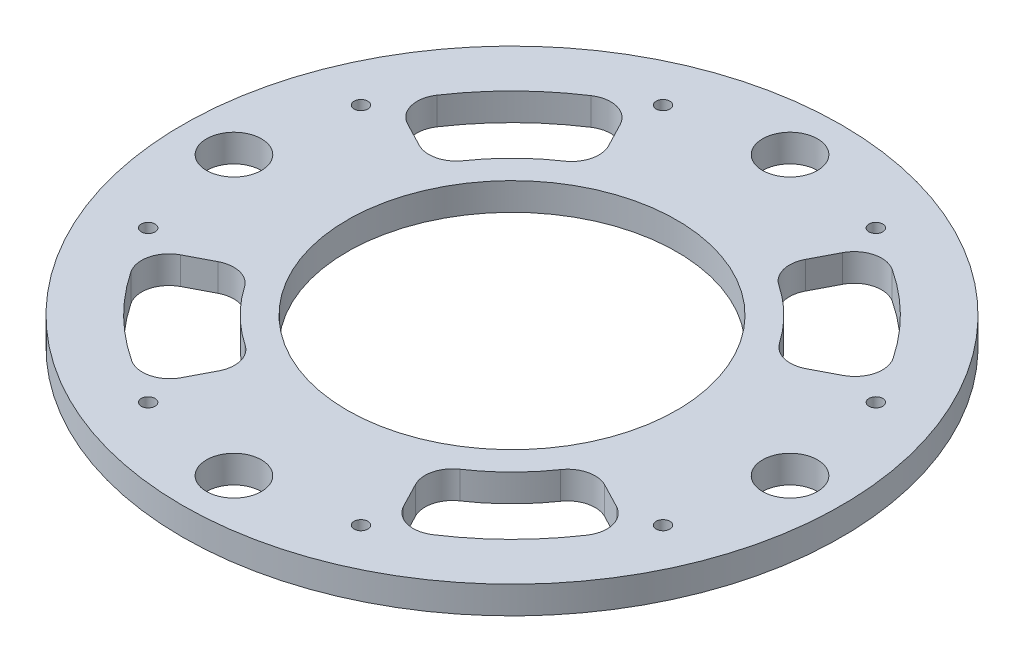
SolidWorks part; units mm, degrees
material "Acrylic (Medium-high impact)"
ref_plane "Front Plane" through (0, 0, 0) normal (0, 0, 1) x (1, 0, 0)
ref_plane "Top Plane" through (0, 0, 0) normal (0, 1, 0) x (1, 0, 0)
ref_plane "Right Plane" through (0, 0, 0) normal (1, 0, 0) x (0, 0, -1)
sketch "Sketch1" plane through (0, 0, 0) normal (0, 1, 0) x (1, 0, 0)
  circle A0 centre (0, 0) radius 76.2
  dimension "D1" = 152.4
extrude "Boss-Extrude1" add sketch "Sketch1" along normal blind 6.35
sketch "Sketch2" plane through (0, 6.35, 0) normal (0, 1, 0) x (1, 0, 0)
  circle A0 centre (0, 0) radius 35
  dimension "D1" = 70
extrude "Cut-Extrude1" cut sketch "Sketch2" against normal blind 6.35
sketch "Sketch3" plane through (0, 6.35, 0) normal (0, 1, 0) x (1, 0, 0)
  line L0 (-76.2, 0) -> (76.2, 0) construction
  line L1 (-51.5875, 51.5875) -> (51.5875, 51.5875) construction
  line L2 (-51.5875, 51.5875) -> (-51.5875, -51.5875) construction
  line L3 (-51.5875, -51.5875) -> (51.5875, -51.5875) construction
  line L4 (51.5875, 51.5875) -> (51.5875, -51.5875) construction
  circle A0 centre (0, 0) radius 76.2 construction
  circle A1 centre (-64.2875, 0) radius 6.35
  circle A2 centre (64.2875, 0) radius 6.35
  dimension "D1" = 12.7
  dimension "D2" = 12.7
  dimension "D3" = 12.7
  dimension "D4" = 12.7
extrude "Cut-Extrude2" cut sketch "Sketch3" against normal blind 10
sketch "Sketch4" plane through (0, 6.35, 0) normal (0, 1, 0) x (1, 0, 0)
  line L1 (50, -50) -> (-50, -50) construction
  line L2 (50, -50) -> (50, 50) construction
  line L3 (50, 50) -> (-50, 50) construction
  line L4 (-50, -50) -> (-50, 50) construction
  line L5 (50, -50) -> (-50, 50) construction
  line L6 (50, 50) -> (-50, -50) construction
  point P0 (0, 0)
  dimension "D1" = 100
  dimension "D2" = 100
sketch "Sketch5" plane through (0, 6.35, 0) normal (0, 1, 0) x (1, 0, 0)
  line L0 (-50, 24.6) -> (-59.525, 24.6) construction
  line L1 (-50, -50) -> (-50, 50) construction
  line L2 (-50, -24.6) -> (-59.525, -24.6) construction
  line L3 (50, 50) -> (-50, 50) construction
  line L4 (50, -50) -> (-50, -50) construction
  line L5 (-50, 50) -> (50, -50) construction
  line L6 (-50, -50) -> (50, 50) construction
  line L7 (24.6, 50) -> (24.6, 59.525) construction
  line L8 (-50, 50) -> (50, 50) construction
  line L9 (-50, 50) -> (-50, -50) construction
  line L10 (-50, -50) -> (50, -50) construction
  line L11 (50, 50) -> (50, -50) construction
  line L12 (-24.6, 50) -> (-24.6, 59.525) construction
  line L13 (50, 24.6) -> (59.525, 24.6) construction
  line L14 (-24.6, -50) -> (-24.6, -59.525) construction
  line L15 (24.6, -50) -> (24.6, -59.525) construction
  line L16 (50, -24.6) -> (59.525, -24.6) construction
  dimension "D1" = 25.4
  dimension "D2" = 25.4
  dimension "D3" = 9.525
  dimension "D4" = 9.525
sketch "Sketch7" plane through (0, 6.35, 0) normal (0, 1, 0) x (1, 0, 0)
  line L0 (0, 0) -> (0, 76.2) construction
  line L1 (0, 0) -> (53.8815, 53.8815) construction
  line L2 (0, 59.5249) -> (-24.5999, 59.5249) construction
  line L3 (0, 0) -> (76.2, 0) construction
  line L4 (0, -59.5249) -> (-24.5999, -59.5249) construction
  circle A0 centre (0, 0) radius 76.2 construction
  circle A1 centre (-24.5999, 59.5249) radius 1.5875
  circle A2 centre (24.5999, 59.5249) radius 1.5875
  circle A3 centre (24.5999, -59.5249) radius 1.5875
  circle A4 centre (-24.5999, -59.5249) radius 1.5875
  circle A5 centre (-59.5249, 24.5999) radius 1.5875
  circle A6 centre (-59.5249, -24.5999) radius 1.5875
  circle A7 centre (59.5249, 24.5999) radius 1.5875
  circle A8 centre (59.5249, -24.5999) radius 1.5875
  dimension "D1" = 45
  dimension "D2" = 59.5249
  dimension "D3" = 24.5999
extrude "Cut-Extrude4" cut sketch "Sketch7" against normal blind 10
sketch "Sketch8" plane through (0, 6.35, 0) normal (0, 1, 0) x (1, 0, 0)
  line L0 (0, 76.2) -> (0, -76.2) construction
  line L1 (0, 0) -> (53.8815, 53.8815) construction
  circle A0 centre (0, 0) radius 76.2 construction
  circle A1 centre (-64.2875, 0) radius 6.35
  circle A2 centre (64.2875, 0) radius 6.35
  circle A3 centre (0, -64.2875) radius 6.35
  circle A4 centre (0, 64.2875) radius 6.35
extrude "Cut-Extrude5" cut sketch "Sketch8" against normal blind 10
sketch "Sketch9" plane through (0, 6.35, 0) normal (0, 1, 0) x (1, 0, 0)
  circle A0 centre (0, 0) radius 38.1
  dimension "D1" = 76.2
extrude "Cut-Extrude6" cut sketch "Sketch9" against normal blind 10
sketch "Sketch10" plane through (0, 6.35, 0) normal (0, 1, 0) x (1, 0, 0)
  line L0 (0, 0) -> (-76.2, 0) construction
  line L1 (0, 0) -> (0, 76.2) construction
  line L2 (0, 0) -> (-53.8815, 53.8815) construction
  line L3 (-22.7447, 45.0673) -> (-25.6934, 50.7318)
  line L4 (-44.7067, 23.2729) -> (-50.3788, 26.2255)
  line L5 (44.7067, 23.2729) -> (50.3788, 26.2255)
  line L6 (22.7447, 45.0673) -> (25.6934, 50.7318)
  line L7 (22.7447, -45.0673) -> (25.6934, -50.7318)
  line L8 (44.7067, -23.2729) -> (50.3788, -26.2255)
  line L9 (-44.7067, -23.2729) -> (-50.3788, -26.2255)
  line L10 (-22.7447, -45.0673) -> (-25.6934, -50.7318)
  circle A0 centre (0, 0) radius 76.2 construction
  arc A1 (-24.83, 36.8683) -> (-36.5528, 25.2922) centre (0, 0) ccw
  arc A2 (-34.8066, 53.1108) -> (-52.7185, 35.3978) centre (0, 0) ccw
  circle A3 centre (0, 0) radius 38.1 construction
  arc A4 (-52.7185, 35.3978) -> (-50.3788, 26.2255) centre (-47.4467, 31.8581) ccw
  arc A5 (-44.7067, 23.2729) -> (-36.5528, 25.2922) centre (-41.7746, 28.9054) ccw
  arc A6 (-24.83, 36.8683) -> (-22.7447, 45.0673) centre (-28.3772, 42.1352) ccw
  arc A7 (-25.6934, 50.7318) -> (-34.8066, 53.1108) centre (-31.3259, 47.7997) ccw
  arc A8 (25.6934, 50.7318) -> (34.8066, 53.1108) centre (31.3259, 47.7997) cw
  arc A9 (24.83, 36.8683) -> (22.7447, 45.0673) centre (28.3772, 42.1352) cw
  arc A10 (44.7067, 23.2729) -> (36.5528, 25.2922) centre (41.7746, 28.9054) cw
  arc A11 (52.7185, 35.3978) -> (50.3788, 26.2255) centre (47.4467, 31.8581) cw
  arc A12 (34.8066, 53.1108) -> (52.7185, 35.3978) centre (0, 0) cw
  arc A13 (24.83, 36.8683) -> (36.5528, 25.2922) centre (0, 0) cw
  arc A14 (24.83, -36.8683) -> (36.5528, -25.2922) centre (0, 0) ccw
  arc A15 (34.8066, -53.1108) -> (52.7185, -35.3978) centre (0, 0) ccw
  arc A16 (52.7185, -35.3978) -> (50.3788, -26.2255) centre (47.4467, -31.8581) ccw
  arc A17 (44.7067, -23.2729) -> (36.5528, -25.2922) centre (41.7746, -28.9054) ccw
  arc A18 (24.83, -36.8683) -> (22.7447, -45.0673) centre (28.3772, -42.1352) ccw
  arc A19 (25.6934, -50.7318) -> (34.8066, -53.1108) centre (31.3259, -47.7997) ccw
  arc A20 (-25.6934, -50.7318) -> (-34.8066, -53.1108) centre (-31.3259, -47.7997) cw
  arc A21 (-24.83, -36.8683) -> (-22.7447, -45.0673) centre (-28.3772, -42.1352) cw
  arc A22 (-44.7067, -23.2729) -> (-36.5528, -25.2922) centre (-41.7746, -28.9054) cw
  arc A23 (-52.7185, -35.3978) -> (-50.3788, -26.2255) centre (-47.4467, -31.8581) cw
  arc A24 (-34.8066, -53.1108) -> (-52.7185, -35.3978) centre (0, 0) cw
  arc A25 (-24.83, -36.8683) -> (-36.5528, -25.2922) centre (0, 0) cw
  circle A26 centre (0, 0) radius 76.2
  dimension "D4" = 6.35
  dimension "D5" = 152.4
  dimension "D6" = 6.35
  dimension "D7" = 12.7
  dimension "D1" = 45
  dimension "D2" = 27.5
  dimension "D3" = 27.5
extrude "Cut-Extrude10" cut sketch "Sketch10" against normal blind 10 contours L3 A7 A2 A4 L4 A5 A1 A6 | A9 A13 A10 L5 A11 A12 A8 L6 | L7 A19 A15 A16 L8 A17 A14 A18 | A21 A25 A22 L9 A23 A24 A20 L10 region at (-37.7369, 6.35, -38.1823) region at (37.7369, 6.35, -38.1823) region at (37.7369, 6.35, 38.1823) region at (-37.7369, 6.35, 38.1823)
sketch "Sketch11" plane through (0, 6.35, 0) normal (0, 1, 0) x (1, 0, 0)
  line L0 (-25.6934, 50.7318) -> (-22.7447, 45.0673)
  line L1 (-44.7067, 23.2729) -> (-50.3788, 26.2255)
  line L4 (44.7067, 23.2729) -> (50.3788, 26.2255)
  line L5 (25.6934, 50.7318) -> (22.7447, 45.0673)
  line L6 (25.6934, -50.7318) -> (22.7447, -45.0673)
  line L7 (44.7067, -23.2729) -> (50.3788, -26.2255)
  line L8 (-44.7067, -23.2729) -> (-50.3788, -26.2255)
  line L9 (-25.6934, -50.7318) -> (-22.7447, -45.0673)
  circle A0 centre (0, 0) radius 38.1
  circle A1 centre (0, 0) radius 76.2
  arc A2 (-24.83, 36.8683) -> (-36.5528, 25.2922) centre (0, 0) ccw
  arc A3 (34.8066, 53.1108) -> (52.7185, 35.3978) centre (0, 0) cw
  circle A4 centre (0, 64.2875) radius 6.5947
  circle A5 centre (-64.2875, 0) radius 6.35
  circle A6 centre (-59.5249, 24.5999) radius 1.5875
  circle A7 centre (-24.5999, 59.5249) radius 1.5875
  arc A8 (-50.3788, 26.2255) -> (-52.7185, 35.3978) centre (-47.4467, 31.8581) cw
  arc A9 (-44.7067, 23.2729) -> (-36.5528, 25.2922) centre (-41.7746, 28.9054) ccw
  arc A10 (-22.7447, 45.0673) -> (-24.83, 36.8683) centre (-28.3772, 42.1352) cw
  arc A11 (-25.6934, 50.7318) -> (-34.8066, 53.1108) centre (-31.3259, 47.7997) ccw
  arc A12 (-34.8066, 53.1108) -> (-52.7185, 35.3978) centre (0, 0) ccw
  arc A13 (25.6934, 50.7318) -> (34.8066, 53.1108) centre (31.3259, 47.7997) cw
  arc A14 (22.7447, 45.0673) -> (24.83, 36.8683) centre (28.3772, 42.1352) ccw
  arc A15 (44.7067, 23.2729) -> (36.5528, 25.2922) centre (41.7746, 28.9054) cw
  arc A16 (50.3788, 26.2255) -> (52.7185, 35.3978) centre (47.4467, 31.8581) ccw
  circle A17 centre (24.5999, 59.5249) radius 1.5875
  circle A18 centre (59.5249, 24.5999) radius 1.5875
  circle A19 centre (64.2875, 0) radius 6.35
  arc A20 (24.83, 36.8683) -> (36.5528, 25.2922) centre (0, 0) cw
  arc A21 (24.83, -36.8683) -> (36.5528, -25.2922) centre (0, 0) ccw
  circle A22 centre (59.5249, -24.5999) radius 1.5875
  circle A23 centre (24.5999, -59.5249) radius 1.5875
  arc A24 (50.3788, -26.2255) -> (52.7185, -35.3978) centre (47.4467, -31.8581) cw
  arc A25 (44.7067, -23.2729) -> (36.5528, -25.2922) centre (41.7746, -28.9054) ccw
  arc A26 (22.7447, -45.0673) -> (24.83, -36.8683) centre (28.3772, -42.1352) cw
  arc A27 (25.6934, -50.7318) -> (34.8066, -53.1108) centre (31.3259, -47.7997) ccw
  arc A28 (34.8066, -53.1108) -> (52.7185, -35.3978) centre (0, 0) ccw
  arc A29 (-34.8066, -53.1108) -> (-52.7185, -35.3978) centre (0, 0) cw
  arc A30 (-25.6934, -50.7318) -> (-34.8066, -53.1108) centre (-31.3259, -47.7997) cw
  arc A31 (-22.7447, -45.0673) -> (-24.83, -36.8683) centre (-28.3772, -42.1352) ccw
  arc A32 (-44.7067, -23.2729) -> (-36.5528, -25.2922) centre (-41.7746, -28.9054) cw
  arc A33 (-50.3788, -26.2255) -> (-52.7185, -35.3978) centre (-47.4467, -31.8581) ccw
  circle A34 centre (-24.5999, -59.5249) radius 1.5875
  circle A35 centre (-59.5249, -24.5999) radius 1.5875
  arc A36 (-24.83, -36.8683) -> (-36.5528, -25.2922) centre (0, 0) cw
  circle A37 centre (0, -64.2875) radius 6.35
